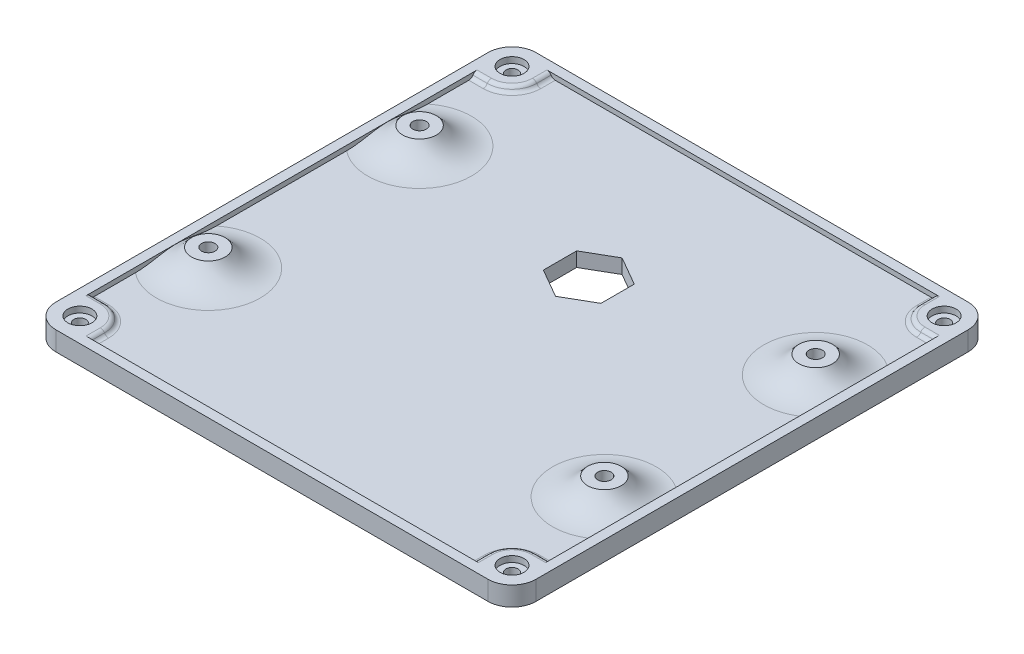
SolidWorks part; units mm, degrees
ref_plane "Front Plane" through (0, 0, 0) normal (0, 0, 1) x (1, 0, 0)
ref_plane "Top Plane" through (0, 0, 0) normal (0, 1, 0) x (1, 0, 0)
ref_plane "Right Plane" through (0, 0, 0) normal (1, 0, 0) x (0, 0, -1)
sketch "Sketch1" plane through (0, 0, 0) normal (0, 1, 0) x (1, 0, 0)
  line L1 (50, 50) -> (-50, 50)
  line L2 (50, 50) -> (50, -50)
  line L3 (50, -50) -> (-50, -50)
  line L4 (-50, 50) -> (-50, -50)
  line L5 (50, 50) -> (-50, -50) construction
  line L6 (50, -50) -> (-50, 50) construction
  point P0 (0, 0)
extrude "Boss-Extrude1" add sketch "Sketch1" along normal blind 4
sketch "Sketch2" plane through (0, 4, 0) normal (0, 1, 0) x (1, 0, 0)
  line L1 (48, 48) -> (-48, 48)
  line L2 (48, 48) -> (48, -48)
  line L3 (48, -48) -> (-48, -48)
  line L4 (-48, 48) -> (-48, -48)
  line L5 (48, 48) -> (-48, -48) construction
  line L6 (48, -48) -> (-48, 48) construction
  point P0 (0, 0)
extrude "Cut-Extrude1" cut sketch "Sketch2" against normal blind 1
sketch "Sketch7" plane through (0, 3, 0) normal (0, 1, 0) x (1, 0, 0)
  line L1 (-48, 48) -> (-40, 48)
  line L2 (-48, 48) -> (-48, 40)
  line L3 (-48, 40) -> (-40, 40)
  line L4 (-40, 48) -> (-40, 40)
  line L5 (-48, 48) -> (-40, 40) construction
  line L6 (-48, 40) -> (-40, 48) construction
  point P0 (-44, 44)
extrude "Boss-Extrude4" add sketch "Sketch7" along normal blind 1
sketch "Sketch9" plane through (0, 3, 0) normal (0, 1, 0) x (1, 0, 0)
  line L1 (48, 48) -> (40, 48)
  line L2 (48, 48) -> (48, 40)
  line L3 (48, 40) -> (40, 40)
  line L4 (40, 48) -> (40, 40)
  line L5 (48, 48) -> (40, 40) construction
  line L6 (48, 40) -> (40, 48) construction
  point P0 (44, 44)
extrude "Boss-Extrude5" add sketch "Sketch9" along normal blind 1
sketch "Sketch10" plane through (0, 3, 0) normal (0, 1, 0) x (1, 0, 0)
  line L1 (-48, -48) -> (-40, -48)
  line L2 (-48, -48) -> (-48, -40)
  line L3 (-48, -40) -> (-40, -40)
  line L4 (-40, -48) -> (-40, -40)
  line L5 (-48, -48) -> (-40, -40) construction
  line L6 (-48, -40) -> (-40, -48) construction
  point P0 (-44, -44)
extrude "Boss-Extrude6" add sketch "Sketch10" along normal blind 1
sketch "Sketch11" plane through (0, 3, 0) normal (0, 1, 0) x (1, 0, 0)
  line L1 (48, -48) -> (40, -48)
  line L2 (48, -48) -> (48, -40)
  line L3 (48, -40) -> (40, -40)
  line L4 (40, -48) -> (40, -40)
  line L5 (48, -48) -> (40, -40) construction
  line L6 (48, -40) -> (40, -48) construction
  point P0 (44, -44)
extrude "Boss-Extrude7" add sketch "Sketch11" along normal blind 1
fillet "Fillet8" radius 5 1 edges at (-40, 3.5, -40)
fillet "Fillet9" radius 5 1 edges at (-40, 3.5, 40)
fillet "Fillet10" radius 5 1 edges at (40, 3.5, 40)
fillet "Fillet11" radius 5 1 edges at (40, 3.5, -40)
fillet "Fillet12" radius 5 1 edges at (50, 2, -50)
fillet "Fillet13" radius 5 1 edges at (50, 2, 50)
fillet "Fillet14" radius 5 1 edges at (-50, 2, 50)
fillet "Fillet15" radius 5 1 edges at (-50, 2, -50)
fillet "Fillet18" radius 1 3 edges at (-40, 3, -46.5) (-46.5, 3, -40) (-41.4645, 3, -41.4645)
fillet "Fillet19" radius 1 3 edges at (-46.5, 4, -40) (-40, 4, -46.5) (-41.4645, 4, -41.4645)
fillet "Fillet20" radius 1 3 edges at (40, 4, -46.5) (46.5, 4, -40) (41.4645, 4, -41.4645)
fillet "Fillet21" radius 1 3 edges at (46.5, 3, -40) (40, 3, -46.5) (41.4645, 3, -41.4645)
fillet "Fillet22" radius 1 3 edges at (-46.5, 3, 40) (-40, 3, 46.5) (-41.4645, 3, 41.4645)
fillet "Fillet23" radius 1 3 edges at (-40, 4, 46.5) (-46.5, 4, 40) (-41.4645, 4, 41.4645)
fillet "Fillet24" radius 1 3 edges at (46.5, 4, 40) (40, 4, 46.5) (41.4645, 4, 41.4645)
fillet "Fillet25" radius 1 3 edges at (40, 3, 46.5) (46.5, 3, 40) (41.4645, 3, 41.4645)
sketch "Sketch15" plane through (0, 4, 0) normal (0, 1, 0) x (1, 0, 0)
  circle A0 centre (-45, 45) radius 2.5
extrude "Cut-Extrude7" cut sketch "Sketch15" against normal blind 1.25
sketch "Sketch16" plane through (0, 0, 0) normal (0, -1, 0) x (1, 0, 0)
  circle A0 centre (-45, -45) radius 2.5
extrude "Cut-Extrude8" cut sketch "Sketch16" against normal blind 1.25
sketch "Sketch17" plane through (0, 2.75, 0) normal (0, 1, 0) x (1, 0, 0)
  circle A0 centre (-45, 45) radius 1.1
extrude "Cut-Extrude9" cut sketch "Sketch17" against normal blind 1.5
sketch "Sketch18" plane through (0, 4, 0) normal (0, 1, 0) x (1, 0, 0)
  circle A0 centre (45, 45) radius 2.5
extrude "Cut-Extrude10" cut sketch "Sketch18" against normal blind 1.25
sketch "Sketch19" plane through (0, 0, 0) normal (0, -1, 0) x (1, 0, 0)
  circle A0 centre (45, -45) radius 2.5
extrude "Cut-Extrude11" cut sketch "Sketch19" against normal blind 1.25
sketch "Sketch20" plane through (0, 2.75, 0) normal (0, 1, 0) x (1, 0, 0)
  circle A0 centre (45, 45) radius 1.05
extrude "Cut-Extrude12" cut sketch "Sketch20" against normal through all
sketch "Sketch21" plane through (0, 4, 0) normal (0, 1, 0) x (1, 0, 0)
  circle A0 centre (-45, -45) radius 2.5
extrude "Cut-Extrude13" cut sketch "Sketch21" against normal blind 1.25
sketch "Sketch23" plane through (0, 0, 0) normal (0, -1, 0) x (-1, 0, 0)
  circle A0 centre (45, -45) radius 2.5
extrude "Cut-Extrude14" cut sketch "Sketch23" against normal blind 1.25
sketch "Sketch24" plane through (0, 2.75, 0) normal (0, 1, 0) x (1, 0, 0)
  circle A0 centre (-45, -45) radius 1.05
extrude "Cut-Extrude15" cut sketch "Sketch24" against normal through all
sketch "Sketch25" plane through (0, 0, 0) normal (0, -1, 0) x (1, 0, 0)
  circle A0 centre (45, 45) radius 2.5
extrude "Cut-Extrude16" cut sketch "Sketch25" against normal blind 1.25
sketch "Sketch26" plane through (0, 4, 0) normal (0, 1, 0) x (1, 0, 0)
  circle A0 centre (45, -45) radius 2.5
extrude "Cut-Extrude17" cut sketch "Sketch26" against normal blind 1.25
sketch "Sketch27" plane through (0, 2.75, 0) normal (0, 1, 0) x (1, 0, 0)
  circle A0 centre (45, -45) radius 1.05
extrude "Cut-Extrude18" cut sketch "Sketch27" against normal through all
sketch "Sketch35" plane through (0, 2.75, 0) normal (0, 1, 0) x (1, 0, 0)
  circle A0 centre (-45, 45) radius 1.25
extrude "Cut-Extrude23" cut sketch "Sketch35" against normal through all
sketch "Sketch36" plane through (0, 2.75, 0) normal (0, 1, 0) x (1, 0, 0)
  circle A0 centre (45, 45) radius 1.25
extrude "Cut-Extrude24" cut sketch "Sketch36" against normal through all
sketch "Sketch37" plane through (0, 2.75, 0) normal (0, 1, 0) x (1, 0, 0)
  circle A0 centre (-45, -45) radius 1.25
extrude "Cut-Extrude25" cut sketch "Sketch37" against normal through all
sketch "Sketch38" plane through (0, 2.75, 0) normal (0, 1, 0) x (1, 0, 0)
  circle A0 centre (45, -45) radius 1.25
extrude "Cut-Extrude26" cut sketch "Sketch38" against normal through all
sketch "Sketch39" plane through (0, 3, 0) normal (0, 1, 0) x (1, 0, 0)
  circle A0 centre (41.25, 22) radius 3.5
  circle A1 centre (-41.25, 22) radius 3.5
  circle A2 centre (-41.25, -22) radius 3.5
  circle A4 centre (41.25, -22) radius 3.5
  circle A5 centre (-41.25, 22) radius 1.4
  circle A6 centre (41.25, 22) radius 1.4
  circle A7 centre (-41.25, -22) radius 1.4
  circle A8 centre (41.25, -22) radius 1.4
extrude "Boss-Extrude12" add sketch "Sketch39" along normal blind 3.75
fillet "Fillet27" radius 9 4 edges at (41.25, 3, -25.5) (41.25, 3, 18.5) (-41.25, 3, 18.5) (-41.25, 3, -25.5)
sketch "Sketch40" plane through (0, 3, 0) normal (0, 1, 0) x (1, 0, 0)
  line L1 (0, 9.0718) -> (6, 12.5359)
  line L2 (6, 12.5359) -> (6, 19.4641)
  line L3 (6, 19.4641) -> (0, 22.9282)
  line L4 (0, 22.9282) -> (-6, 19.4641)
  line L5 (-6, 19.4641) -> (-6, 12.5359)
  line L6 (-6, 12.5359) -> (0, 9.0718)
  circle A0 centre (0, 16) radius 6 construction
extrude "Cut-Extrude27" cut sketch "Sketch40" against normal through all
